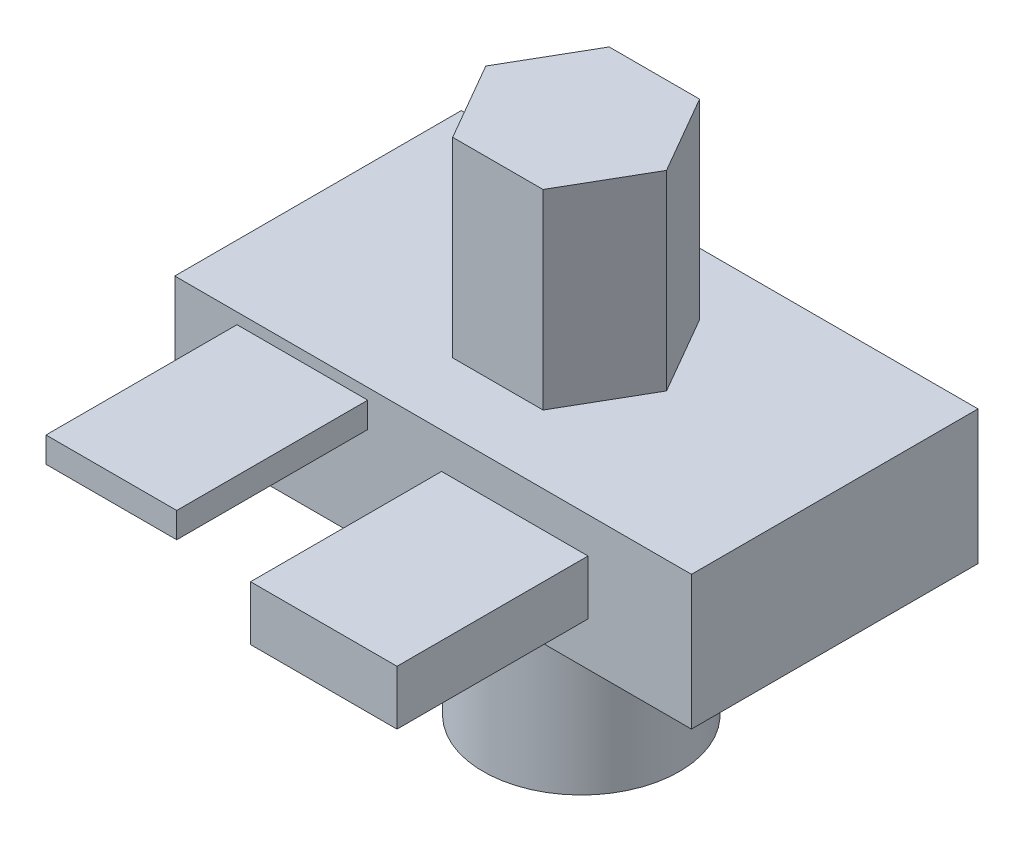
SolidWorks part; units mm, degrees
ref_plane "Front Plane" through (0, 0, 0) normal (0, 0, 1) x (1, 0, 0)
ref_plane "Top Plane" through (0, 0, 0) normal (0, 1, 0) x (1, 0, 0)
ref_plane "Right Plane" through (0, 0, 0) normal (1, 0, 0) x (0, 0, -1)
sketch "Sketch1" plane through (0, 0, 0) normal (0, 0, 1) x (1, 0, 0)
  line L1 (-68.7035, -17.821) -> (68.7035, -17.821)
  line L2 (-68.7035, -17.821) -> (-68.7035, 17.821)
  line L3 (-68.7035, 17.821) -> (68.7035, 17.821)
  line L4 (68.7035, -17.821) -> (68.7035, 17.821)
  line L5 (-68.7035, -17.821) -> (68.7035, 17.821) construction
  line L6 (-68.7035, 17.821) -> (68.7035, -17.821) construction
  point P0 (0, 0)
extrude "Boss-Extrude1" add sketch "Sketch1" along normal blind 76.2 contours L1 L4 L3 L2
sketch "Sketch2" plane through (0, 17.821, 0) normal (0, 1, 0) x (1, 0, 0)
  line L1 (23.159, -37.2907) -> (11.1437, -16.4796)
  line L2 (11.1437, -16.4796) -> (-12.8869, -16.4796)
  line L3 (-12.8869, -16.4796) -> (-24.9022, -37.2907)
  line L4 (-24.9022, -37.2907) -> (-12.8869, -58.1018)
  line L5 (-12.8869, -58.1018) -> (11.1437, -58.1018)
  line L6 (11.1437, -58.1018) -> (23.159, -37.2907)
  circle A0 centre (-0.8716, -37.2907) radius 20.8111 construction
extrude "Boss-Extrude2" add sketch "Sketch2" along normal blind 50.8
sketch "Sketch3" plane through (0, -17.821, 0) normal (0, -1, 0) x (1, 0, 0)
  circle A0 centre (0, 36.7926) radius 26.0998
extrude "Boss-Extrude3" add sketch "Sketch3" along normal blind 50.8
sketch "Sketch4" plane through (0, 0, 76.2) normal (0, 0, 1) x (1, 0, 0)
  line L1 (-52.1439, 14.8868) -> (-17.3813, 14.8868)
  line L2 (-52.1439, 14.8868) -> (-52.1439, 8.1274)
  line L3 (-52.1439, 8.1274) -> (-17.3813, 8.1274)
  line L4 (-17.3813, 14.8868) -> (-17.3813, 8.1274)
  line L5 (-52.1439, 14.8868) -> (-17.3813, 8.1274) construction
  line L6 (-52.1439, 8.1274) -> (-17.3813, 14.8868) construction
  line L7 (2.2531, 8.2883) -> (41.2001, 8.2883)
  line L8 (2.2531, 8.2883) -> (2.2531, -6.1961)
  line L9 (2.2531, -6.1961) -> (41.2001, -6.1961)
  line L10 (41.2001, 8.2883) -> (41.2001, -6.1961)
  line L11 (2.2531, 8.2883) -> (41.2001, -6.1961) construction
  line L12 (2.2531, -6.1961) -> (41.2001, 8.2883) construction
  point P0 (-34.7626, 11.5071)
  point P5 (21.7266, 1.0461)
extrude "Boss-Extrude4" add sketch "Sketch4" along normal blind 50.8
